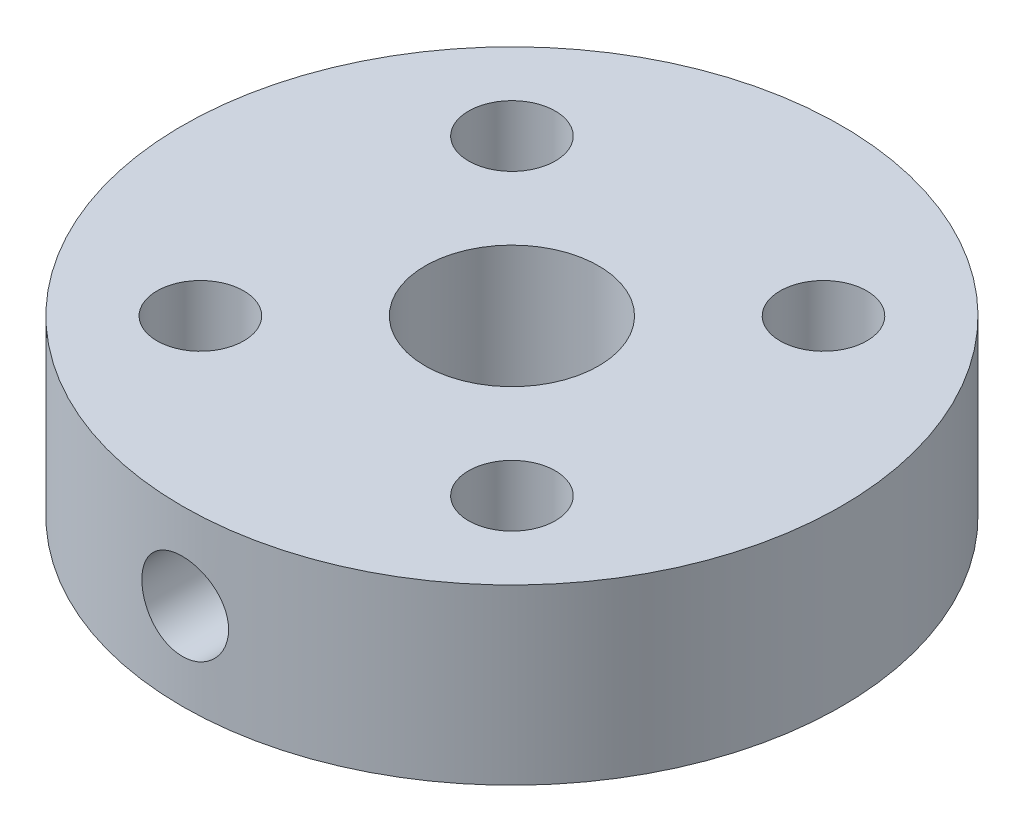
SolidWorks part; units mm, degrees
ref_plane "Front" through (0, 0, 0) normal (0, 0, 1) x (1, 0, 0)
ref_plane "Top" through (0, 0, 0) normal (0, 1, 0) x (1, 0, 0)
ref_plane "Right" through (0, 0, 0) normal (1, 0, 0) x (0, 0, -1)
sketch "Sketch1" plane through (0, 0, 0) normal (0, 1, 0) x (1, 0, 0)
  circle A0 centre (0, 0) radius 9.5
  dimension "D1" = 19
extrude "Boss-Extrude1" add sketch "Sketch1" along normal blind 5
hole_wizard "Ø5.0mm Dowel Hole1" positions "Sketch2" profile "Sketch3" hole size "Ø5.0" standard "ANSI Metric" end condition through all
sketch "Sketch2" plane through (0, 5, 0) normal (0, 1, 0) x (1, 0, 0)
  point P0 (0, 0)
sketch "Sketch3" plane through (0, 5, 0) normal (1, 0, 0) x (0, 0, 1)
  line L0 (0, 0) -> (0, 5)
  line L1 (0, 5) -> (2.5, 5)
  line L2 (2.5, 5) -> (2.5, 0)
  line L5 (2.5, 0) -> (0, 0)
  line L11 (0, -6.35) -> (0, 107.95) construction
  dimension "Thru Hole Dia." = 5
  dimension "Thru Hole Depth" = 5
hole_wizard "M3x0.5 Tapped Hole1" positions "Sketch4" profile "Sketch5" tap size "M3x0.5" standard "ANSI Metric" end condition through all
sketch "Sketch4" plane through (0, 5, 0) normal (0, 1, 0) x (1, 0, 0)
  line L0 (0, 0) -> (4.4901, 4.4901) construction
  line L3 (0, 0) -> (-4.4901, 4.4901) construction
  line L6 (0, 0) -> (-4.4901, -4.4901) construction
  line L9 (0, 0) -> (4.4901, -4.4901) construction
  line L10 (0, 0) -> (4.8926, 0) construction
  point P0 (4.4901, 4.4901)
  point P2 (-4.4901, 4.4901)
  point P4 (-4.4901, -4.4901)
  point P6 (4.4901, -4.4901)
  dimension "D1" = 45
  dimension "D2" = 6.35
  dimension "D3" = 90
sketch "Sketch5" plane through (4.4901, 5, -4.4901) normal (1, 0, 0) x (0, 0, 1)
  line L0 (0, 0) -> (0, 5)
  line L1 (0, 5) -> (1.25, 5)
  line L2 (1.25, 5) -> (1.25, 0)
  line L5 (1.25, 0) -> (0, 0)
  line L11 (0, -6.35) -> (0, 107.95) construction
  dimension "Thru Tap Drill Dia." = 2.5
  dimension "Thru Tap Drill Depth" = 5
cosmetic thread "Hole Thread1" parameters "D2"=3
cosmetic thread "Hole Thread2" parameters "D2"=3
cosmetic thread "Hole Thread3" parameters "D2"=3
cosmetic thread "Hole Thread4" parameters "D2"=3
hole_wizard "M3x0.5 Tapped Hole2" positions "3DSketch1" profile "Sketch7" tap size "M3x0.5" standard "ANSI Metric"
sketch3d "3DSketch1"
  line L2 (0, 0, 0) -> (0, 2.5, 0) construction
  point P0 (0, 2.5, 9.5)
  dimension "D1" = 2.5
sketch "Sketch7" plane through (0, 2.5, 9.5) normal (1, 0, 0) x (0, -1, 0)
  line L0 (0, 0) -> (0, 10.7511)
  line L1 (0, 10.7511) -> (1.25, 10)
  line L2 (1.25, 10) -> (1.25, 0)
  line L5 (1.25, 0) -> (0, 0)
  line L10 (0, 10.7511) -> (-1.25, 10) construction
  line L11 (0, -6.35) -> (0, 107.95) construction
  dimension "Tap Drill Dia." = 2.5
  dimension "Tap Drill Depth" = 10
  dimension "Drill Angle" = 118
cosmetic thread "Hole Thread5" parameters "D1"=10, "D2"=3
